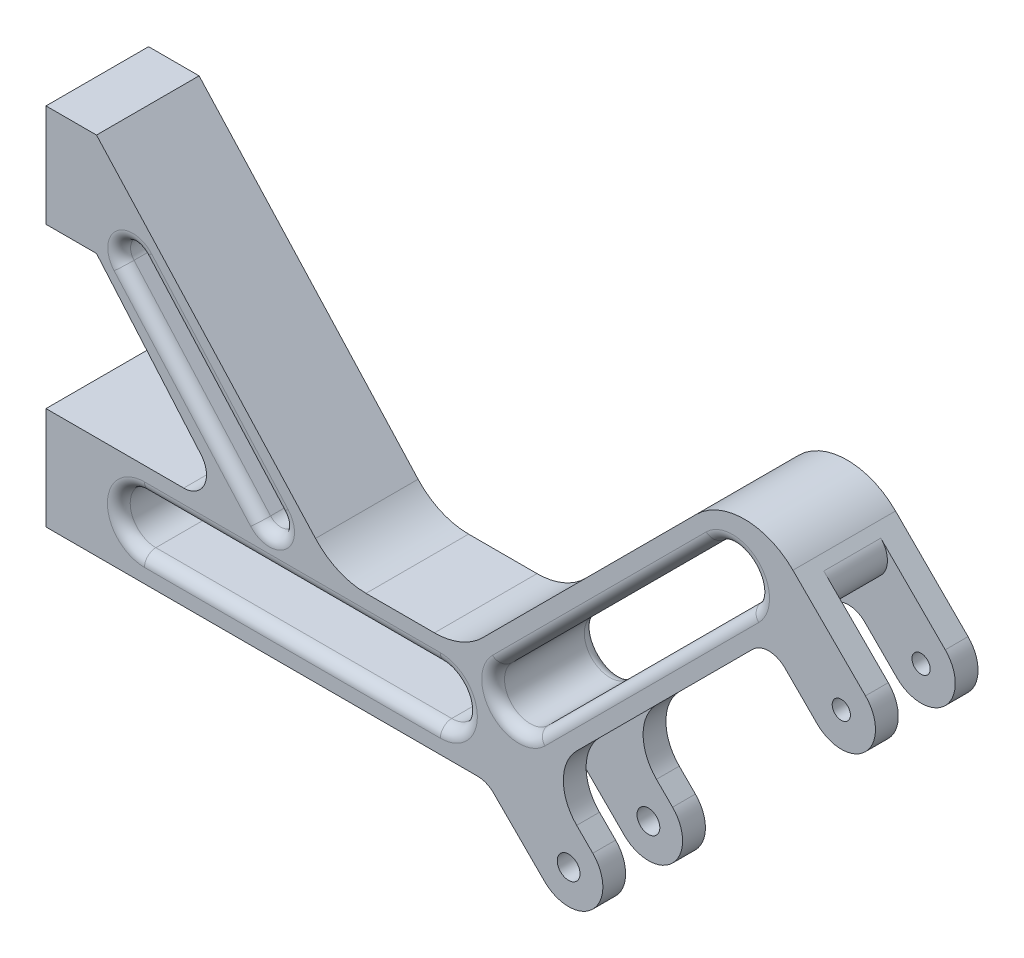
SolidWorks part; units mm, degrees
material "6061 Alloy"
ref_plane "Front Plane" through (0, 0, 0) normal (0, 0, 1) x (1, 0, 0)
ref_plane "Top Plane" through (0, 0, 0) normal (0, 1, 0) x (1, 0, 0)
ref_plane "Right Plane" through (0, 0, 0) normal (1, 0, 0) x (0, 0, -1)
sketch "Sketch1" plane through (0, 0, 0) normal (1, 0, 0) x (0, 0, -1)
  line L1 (-20, 20) -> (20, 20)
  line L2 (-20, 20) -> (-20, -20)
  line L3 (-20, -20) -> (20, -20)
  line L4 (20, 20) -> (20, -20) construction
  line L5 (-20, 20) -> (20, -20) construction
  line L6 (-20, -20) -> (20, 20) construction
  line L7 (-22.5, 22.5) -> (22.5, 22.5)
  line L8 (-22.5, 22.5) -> (-22.5, -22.5)
  line L9 (-22.5, -22.5) -> (22.5, -22.5)
  line L10 (22.5, 22.5) -> (22.5, -22.5)
  line L11 (-22.5, 22.5) -> (22.5, -22.5) construction
  line L12 (-22.5, -22.5) -> (22.5, 22.5) construction
  point P0 (0, 0)
  point P6 (0, 0)
  dimension "D1" = 40
  dimension "D2" = 40
  dimension "D3" = 45
  dimension "D4" = 45
sketch "Sketch2" plane through (0, 0, 0) normal (0, 0, 1) x (1, 0, 0)
  line L0 (0, 0) -> (170, 0)
  line L1 (300.2297, 0) -> (300.2297, 130.2297) construction
  line L2 (300.2297, 35.5495) -> (173.2297, 35.5495) construction
  line L3 (300.2297, 130.2297) -> (170, 0)
  line L4 (170, 0) -> (300.2297, 0) construction
  line L5 (300.2297, 130.2297) -> (347.9594, 82.5)
  line L6 (347.9594, 82.5) -> (326.7462, 61.2868)
  line L7 (326.7462, 61.2868) -> (279.0165, 109.0165)
  line L8 (337.3528, 71.8934) -> (324.9741, 84.2721) construction
  line L9 (326.7462, 82.5) -> (326.7462, 0) construction
  line L10 (300.2297, 0) -> (326.7462, 0)
  line L11 (82.5, 22.5) -> (82.5, 37.8458) construction
  line L12 (0, 22.5) -> (92.0876, 22.5)
  line L13 (0, 22.5) -> (0, -22.5) construction
  line L14 (0, 22.5) -> (0, -22.5) construction
  line L15 (82.5, 22.5) -> (0, 105)
  line L16 (0, 22.5) -> (0, 105) construction
  arc A0 (34.4369, 70.5631) -> (25.2297, 0) centre (300.2297, 0) ccw construction
  circle A1 centre (326.7462, 82.5) radius 5.9071
  dimension "D2" = 550
  dimension "D7" = 15
  dimension "D4" = 82.5
  dimension "D1" = 170
  dimension "D3" = 135
  dimension "D5" = 30
  dimension "D6" = 67.5
  dimension "D8" = 82.5
  dimension "D9" = 45
sweep "Sweep1" add profiles "Sketch1" path "Sketch2"
sketch "Sketch5" plane through (0, 0, 22.5) normal (0, 0, 1) x (1, 0, 0)
  line L0 (170, 0) -> (217.7297, -47.7297) construction
  line L1 (179.3198, -22.5) -> (160.6802, 22.5) construction
  line L2 (179.3198, -22.5) -> (0, -22.5) construction
  line L3 (207.1231, -58.3363) -> (159.3934, -10.6066)
  line L4 (159.3934, -10.6066) -> (180.6066, 10.6066)
  line L5 (207.1231, -58.3363) -> (228.3363, -37.1231)
  line L6 (228.3363, -37.1231) -> (180.6066, 10.6066)
  line L7 (170, 0) -> (0, 0) construction
  line L8 (170, 0) -> (279.0165, 109.0165) construction
  line L9 (284.3198, 146.1396) -> (316.1396, 114.3198) construction
  line L10 (300.2297, 130.2297) -> (347.9594, 82.5)
  line L11 (347.9594, 82.5) -> (326.7462, 61.2868)
  line L12 (326.7462, 61.2868) -> (279.0165, 109.0165)
  line L13 (337.3528, 71.8934) -> (318.0612, 91.185) construction
  line L14 (300.2297, 130.2297) -> (279.0165, 109.0165)
  circle A0 centre (207.1231, -37.1231) radius 5
  circle A1 centre (326.7462, 82.5) radius 4
  point P9 (217.7297, -47.7297)
  point P14 (170, 0)
  dimension "D4" = 10
  dimension "D5" = 15
  dimension "D8" = 8
  dimension "D9" = 15
  dimension "D1" = 135
  dimension "D2" = 67.5
  dimension "D3" = 30
  dimension "D6" = 67.5
  dimension "D7" = 30
  dimension "D10" = 154.1726
extrude "Boss-Extrude2" add sketch "Sketch5" against normal blind 10
fillet "Fillet2" radius 15 4 edges at (207.1231, -58.3363, 17.5) (228.3363, -37.1231, 17.5) (326.7462, 61.2868, 17.5) (347.9594, 82.5, 17.5)
mirror "Mirror1" about plane through (0, 0, 0) normal (0, 0, 1) of "Boss-Extrude2", "Fillet2"
sketch "Sketch6" plane through (0, 22.5, 0) normal (0, 1, 0) x (1, 0, 0)
  line L0 (0, 0) -> (170, 0) construction
  line L1 (60, 22.5) -> (105, 22.5)
  line L2 (60, 22.5) -> (60, -22.5)
  line L3 (60, -22.5) -> (105, -22.5)
  line L4 (105, 22.5) -> (105, -22.5)
  line L5 (60, 22.5) -> (105, -22.5) construction
  line L6 (60, -22.5) -> (105, 22.5) construction
  line L7 (160.6802, -22.5) -> (0, -22.5) construction
  line L8 (0, 22.5) -> (0, -22.5) construction
  point P0 (82.5, 0)
  dimension "D1" = 60
sketch "Sketch7" plane through (0, 0, 0) normal (-1, 0, 0) x (0, 0, 1)
  line L0 (0, 130.2297) -> (0, 82.5) construction
  line L1 (-22.5, 137.5) -> (22.5, 137.5)
  line L2 (-22.5, 137.5) -> (-22.5, 92.5)
  line L3 (-22.5, 92.5) -> (22.5, 92.5)
  line L4 (22.5, 137.5) -> (22.5, 92.5)
  line L5 (-22.5, 137.5) -> (22.5, 92.5) construction
  line L6 (-22.5, 92.5) -> (22.5, 137.5) construction
  line L7 (22.5, 22.5) -> (-22.5, 22.5) construction
  point P0 (0, 115)
  point P16 (22.5, -22.5)
  dimension "D1" = 45
  dimension "D2" = 70
loft "Loft1" add profiles "Sketch6", "Sketch7" connector at (105, 22.5, -22.5) connector at (0, 137.5, -22.5)
fillet "Fillet3" radius 10 5 edges at (294.9264, 93.1066, 17.5) (294.9264, 93.1066, -17.5) (171.2868, -22.5, -17.5) (171.2868, -22.5, 17.5) tangent propagation no
fillet "Fillet4" radius 30 1 edges at (284.3198, 146.1396, 0)
fillet "Fillet5" radius 30 1 edges
sketch "Sketch8" plane through (0, 0, 22.5) normal (0, 0, 1) x (1, 0, 0)
  line L0 (21.0386, 0) -> (150.8392, 0) construction
  line L1 (0, 0) -> (170, 0) construction
  line L2 (21.0386, 11.25) -> (150.8392, 11.25)
  line L3 (21.0386, -11.25) -> (150.8392, -11.25)
  line L4 (185.2441, 15.2441) -> (279.0165, 109.0165) construction
  line L5 (300.2297, 130.2297) -> (170, 0) construction
  line L6 (177.2891, 23.1991) -> (271.0616, 116.9715)
  line L7 (193.1991, 7.2891) -> (286.9715, 101.0616)
  line L8 (0, 115) -> (82.5, 22.5) construction
  line L9 (0, 92.5) -> (0, 137.5) construction
  line L10 (15.9385, 97.1295) -> (82.5, 22.5) construction
  line L11 (20.4163, 101.1232) -> (86.9778, 26.4937)
  line L12 (11.4607, 93.1359) -> (78.0222, 18.5063)
  line L13 (82.5, 22.5) -> (75.8439, 29.963)
  arc A0 (21.0386, 11.25) -> (21.0386, -11.25) centre (21.0386, 0) ccw
  arc A1 (150.8392, -11.25) -> (150.8392, 11.25) centre (150.8392, 0) ccw
  arc A2 (177.2891, 23.1991) -> (193.1991, 7.2891) centre (185.2441, 15.2441) ccw
  arc A3 (286.9715, 101.0616) -> (271.0616, 116.9715) centre (279.0165, 109.0165) ccw
  arc A4 (20.4163, 101.1232) -> (11.4607, 93.1359) centre (15.9385, 97.1295) ccw
  arc A5 (78.0222, 18.5063) -> (86.9778, 26.4937) centre (82.5, 22.5) ccw
  arc A6 (71.3661, 25.9693) -> (80.3216, 33.9566) centre (75.8439, 29.963) ccw
  point P4 (85.9389, 0)
  point P9 (232.1303, 62.1303)
  point P25 (49.2193, 59.8148)
  dimension "D1" = 11.25
  dimension "D2" = 11.25
  dimension "D3" = 6
  dimension "D4" = 100
  dimension "D5" = 10
extrude "Cut-Extrude1" cut sketch "Sketch8" against normal through all contours L7 A3 L6 A2 | L12 A6 L11 A4 | L3 A1 L2 A0 region at (232.1303, 62.1303, 22.5) region at (45.8912, 63.5462, 22.5)
fillet "Fillet6" radius 5 20 edges at (41.4134, 59.5526, 22.5) (11.9448, 101.6073, 22.5) (50.369, 67.5399, 22.5) (240.0853, 54.1754, 22.5) (177.2891, 7.2891, 22.5) (224.1754, 70.0853, 22.5) (162.0892, 0, 22.5) (85.9389, -11.25, 22.5) (9.7886, 0, 22.5) (9.7886, 0, -22.5) (85.9389, 11.25, -22.5) (162.0892, 0, -22.5) (177.2891, 7.2891, -22.5) (224.1754, 70.0853, -22.5) (286.9715, 116.9715, -22.5) (286.9715, 116.9715, 22.5) (85.9389, 11.25, 22.5) (85.9389, -11.25, -22.5) (240.0853, 54.1754, -22.5) (79.8375, 25.4852, 22.5)
fillet "Fillet7" radius 20 2 edges at (196.5165, -5.3033, 17.5) (196.5165, -5.3033, -17.5)
fillet "Fillet8" radius 25 1 edges at (179.3198, -22.5, 0)
fillet "Fillet10" radius 5 4 edges at (11.9448, 101.6073, -22.5) (41.4134, 59.5526, -22.5) (79.8375, 25.4852, -22.5) (50.369, 67.5399, -22.5)
fillet "Fillet11" radius 10 1 edges at (316.1396, 114.3198, 0)
fillet "Fillet12" radius 30 1 edges at (160.6802, 22.5, 0)
sketch "Sketch9" plane through (0, 0, 0) normal (-1, 0, 0) x (0, 0, 1)
  line L1 (-22.5, 22.5) -> (22.5, 22.5)
  line L2 (-22.5, 22.5) -> (-22.5, -22.5)
  line L3 (-22.5, -22.5) -> (22.5, -22.5)
  line L4 (22.5, 22.5) -> (22.5, -22.5)
  line L5 (-22.5, 137.5) -> (22.5, 137.5)
  line L6 (-22.5, 137.5) -> (-22.5, 92.5)
  line L7 (-22.5, 92.5) -> (22.5, 92.5)
  line L8 (22.5, 137.5) -> (22.5, 92.5)
extrude "Boss-Extrude3" add sketch "Sketch9" along normal blind 22.16
